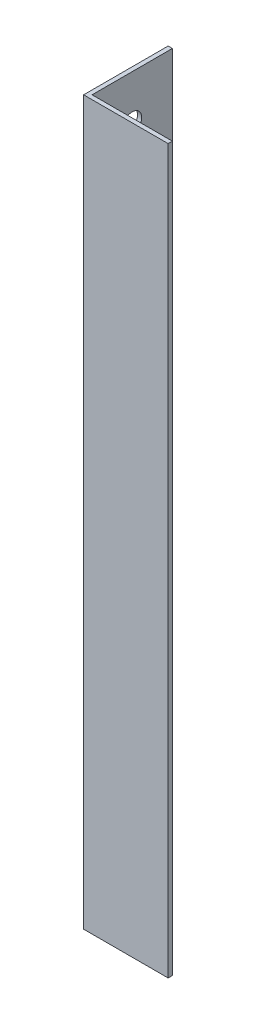
SolidWorks part; units mm, degrees
material "1060 Сплав"
ref_plane "Спереди" through (0, 0, 0) normal (0, 0, 1) x (1, 0, 0)
ref_plane "Сверху" through (0, 0, 0) normal (0, 1, 0) x (1, 0, 0)
ref_plane "Справа" through (0, 0, 0) normal (1, 0, 0) x (0, 0, -1)
sketch "Эскиз1" plane through (0, 0, 0) normal (0, 1, 0) x (1, 0, 0)
  line L0 (0, 0) -> (0, 20)
  line L1 (0, 20) -> (1, 20)
  line L2 (1, 20) -> (1, 1)
  line L3 (1, 1) -> (20, 1)
  line L4 (20, 1) -> (20, 0)
  line L5 (20, 0) -> (0, 0)
  dimension "D1" = 1
  dimension "D2" = 20
extrude "Бобышка-Вытянуть1" add sketch "Эскиз1" along normal blind 171
sketch "Эскиз2" plane through (1, 0, 0) normal (1, 0, 0) x (0, 0, -1)
  circle A0 centre (10.5, 9.5) radius 2.25 construction
  circle A1 centre (10.5, 9.5) radius 2.25
  circle A2 centre (10.5, 160.5) radius 2.25 construction
  circle A3 centre (10.5, 160.5) radius 2.25
extrude "Вырез-Вытянуть1" cut sketch "Эскиз2" against normal through all
